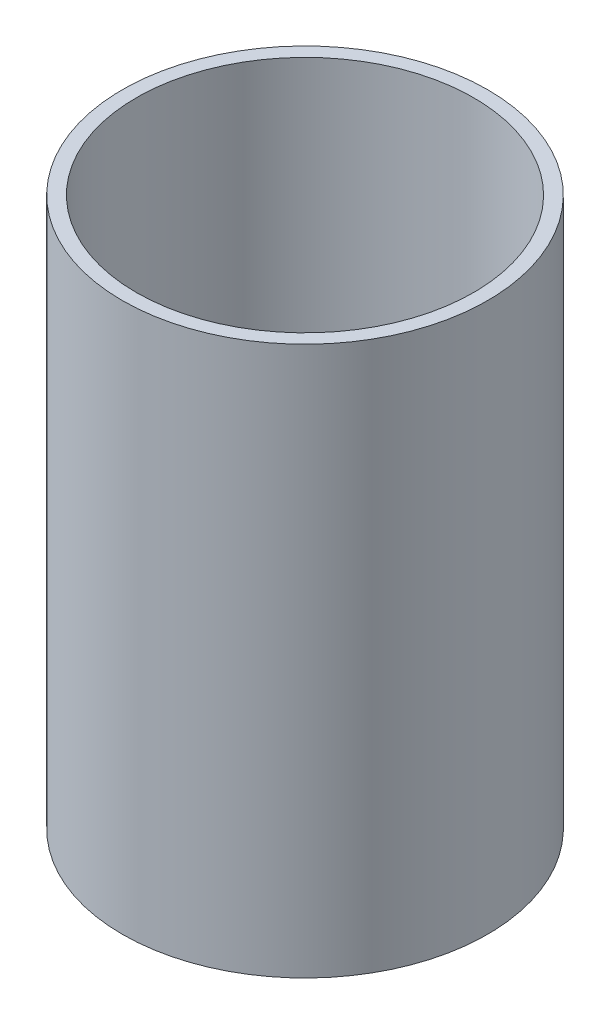
SolidWorks part; units mm, degrees
material "AISI 304"
ref_plane "Front Plane" through (0, 0, 0) normal (0, 0, 1) x (1, 0, 0)
ref_plane "Top Plane" through (0, 0, 0) normal (0, 1, 0) x (1, 0, 0)
ref_plane "Right Plane" through (0, 0, 0) normal (1, 0, 0) x (0, 0, -1)
sketch "Sketch1" plane through (0, 0, 0) normal (0, 0, 1) x (1, 0, 0)
  line L0 (9.525, 0) -> (10.3124, 0)
  line L1 (10.3124, 0) -> (10.3124, 30.988)
  line L2 (10.3124, 30.988) -> (9.525, 30.988)
  line L3 (9.525, 30.988) -> (9.525, 0)
  line L4 (0, 0) -> (0, 30.988) construction
revolve "Revolve1" add sketch "Sketch1" angle 360 about L4 reverse direction yes
ref_plane "Plane1" through (0, 30.988, 0) normal (0, 1, 0) x (1, 0, 0)
ref_plane "tube_rear XY" through (0, 30.988, 0) normal (0, 1, 0) x (1, 0, 0)
ref_plane "tube_rear XZ" through (0, 0, 0) normal (0, 0, 1) x (1, 0, 0)
ref_plane "tube_rear YZ" through (0, 0, 0) normal (1, 0, 0) x (0, 0, -1)
ref_axis "tube_rear X" through (-80.9, 30.988, 0) along (1, 0, 0)
ref_axis "tube_rear Y" through (0, 30.988, 50) along (0, 0, -1)
ref_axis "tube_rear Z" through (0, 50, 0) along (0, -1, 0)
sketch3d "tube_rear"
  point P0 (0, 30.988, 0)
ref_plane "tube_rod_guide XY" through (0, 0, 0) normal (0, 1, 0) x (1, 0, 0)
ref_plane "tube_rod_guide XZ" through (0, 0, 0) normal (0, 0, 1) x (1, 0, 0)
ref_plane "tube_rod_guide YZ" through (0, 0, 0) normal (1, 0, 0) x (0, 0, -1)
ref_axis "tube_rod_guide X" through (-80.9, 0, 0) along (1, 0, 0)
ref_axis "tube_rod_guide Y" through (0, 0, 50) along (0, 0, -1)
ref_axis "tube_rod_guide Z" through (0, 50, 0) along (0, -1, 0)
sketch3d "tube_rod_guide"
  point P0 (0, 0, 0)
